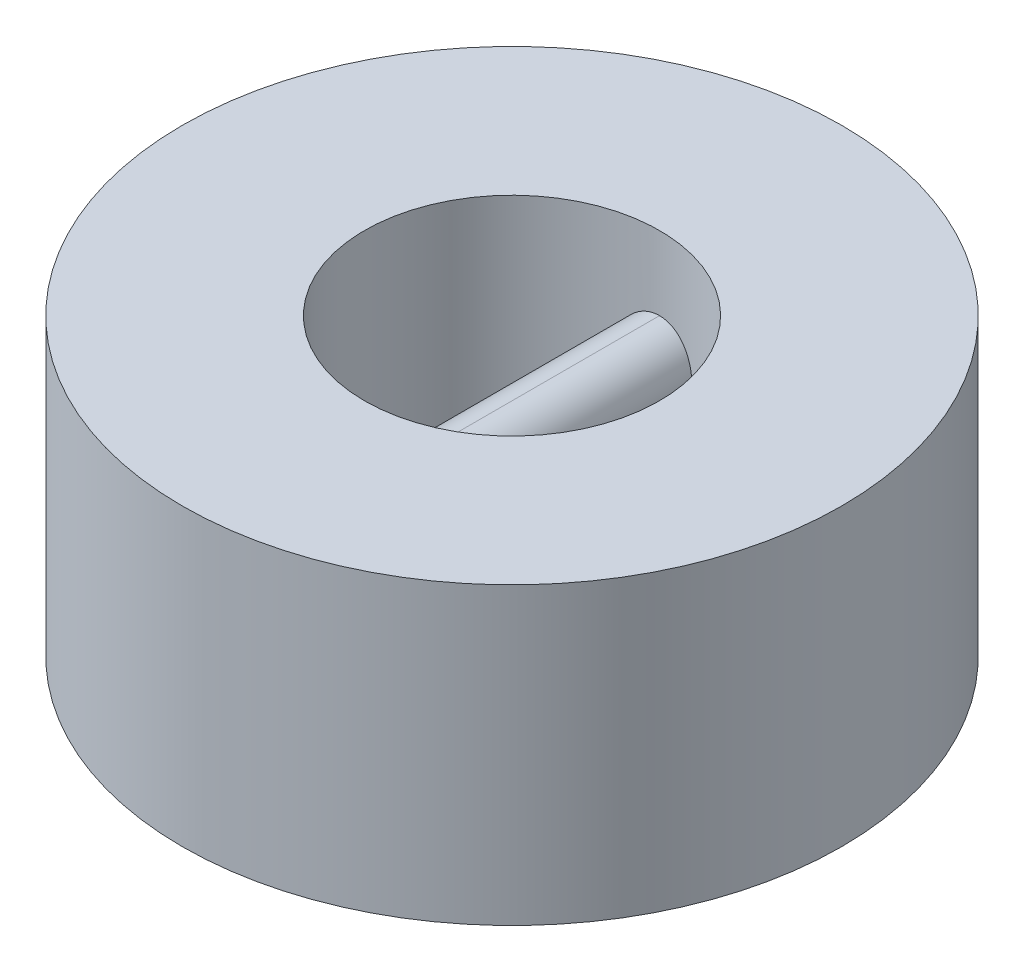
SolidWorks part; units mm, degrees
ref_plane "Front Plane" through (0, 0, 0) normal (0, 0, 1) x (1, 0, 0)
ref_plane "Top Plane" through (0, 0, 0) normal (0, 1, 0) x (1, 0, 0)
ref_plane "Right Plane" through (0, 0, 0) normal (1, 0, 0) x (0, 0, -1)
sketch "Sketch1" plane through (0, 0, 0) normal (0, 1, 0) x (1, 0, 0)
  circle A0 centre (0, 0) radius 56.7646
extrude "Boss-Extrude1" add sketch "Sketch1" along normal mid plane 50.8
sketch "Sketch3" plane through (0, 0, 0) normal (0, 1, 0) x (1, 0, 0)
  circle A0 centre (0, 0) radius 25.4
  dimension "D1" = 50.8
extrude "Cut-Extrude1" cut sketch "Sketch3" along normal through all both and the other way through all
sketch "Sketch4" plane through (0, 0, 0) normal (0, 1, 0) x (1, 0, 0)
  line L0 (-6.35, -25.4) -> (-6.35, 25.4)
  line L1 (-6.35, -25.4) -> (6.35, -25.4)
  line L2 (-6.35, 25.4) -> (6.35, 25.4)
  line L3 (6.35, -25.4) -> (6.35, 25.4)
  line L4 (-6.35, -25.4) -> (6.35, 25.4) construction
  line L5 (-6.35, 25.4) -> (6.35, -25.4) construction
  point P1 (0, 0)
  dimension "D1" = 12.7
  dimension "D2" = 50.8
extrude "Boss-Extrude2" add sketch "Sketch4" along normal blind 12.7
fillet "Fillet1" radius 6.35 4 edges at (-6.35, 0, 0) (-6.35, 12.7, 0) (6.35, 0, 0) (6.35, 12.7, 0)
